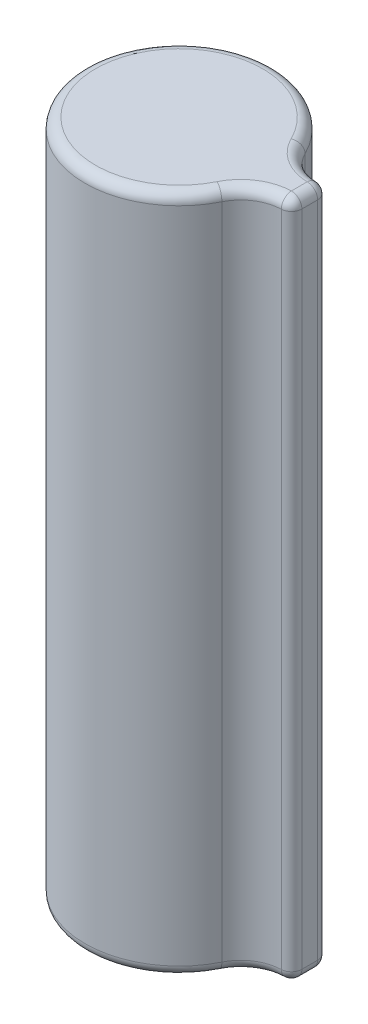
SolidWorks part; units mm, degrees
ref_plane "前视基准面" through (0, 0, 0) normal (0, 0, 1) x (1, 0, 0)
ref_plane "上视基准面" through (0, 0, 0) normal (0, 1, 0) x (1, 0, 0)
ref_plane "右视基准面" through (0, 0, 0) normal (1, 0, 0) x (0, 0, -1)
other "Configuration Table"
sketch "草图1" plane through (0, 0, 0) normal (0, 1, 0) x (1, 0, 0)
  line L0 (5.6226, 0) -> (20.6859, 0) construction
  line L1 (5.8962, 1.75) -> (12.5, 1.75)
  line L2 (5.8962, 1.75) -> (5.8962, -1.75)
  line L3 (5.8962, -1.75) -> (12.5, -1.75)
  line L4 (12.5, 1.75) -> (12.5, -1.75)
  line L5 (9, 5.6881) -> (9, -6.615) construction
  circle A0 centre (0, 0) radius 9
  dimension "D1" = 18
  dimension "D2" = 3.5
  dimension "D3" = 3.5
extrude "凸台-拉伸1" add sketch "草图1" along normal blind 65 contours L1 A0 L3 L2 | L3 A0 L1 L2 | A0 L3 L4 L1
fillet "圆角1" radius 4 2 edges at (8.8282, 32.5, -1.75) (8.8282, 32.5, 1.75)
fillet "圆角2" radius 1 2 edges at (12.5, 32.5, 1.75) (12.5, 32.5, -1.75)
fillet "圆角3" radius 1 12 edges at (12.2183, 0, -1.4483) (9.4932, 0, -2.3872) (-9, 0, 0) (9.4932, 0, 2.3872) (12.2183, 0, 1.4483) (12.5, 0, 0) (-9, 65, 0) (9.4932, 65, -2.3872) (12.2183, 65, -1.4483) (12.5, 65, 0) (12.2183, 65, 1.4483) (9.4932, 65, 2.3872)
